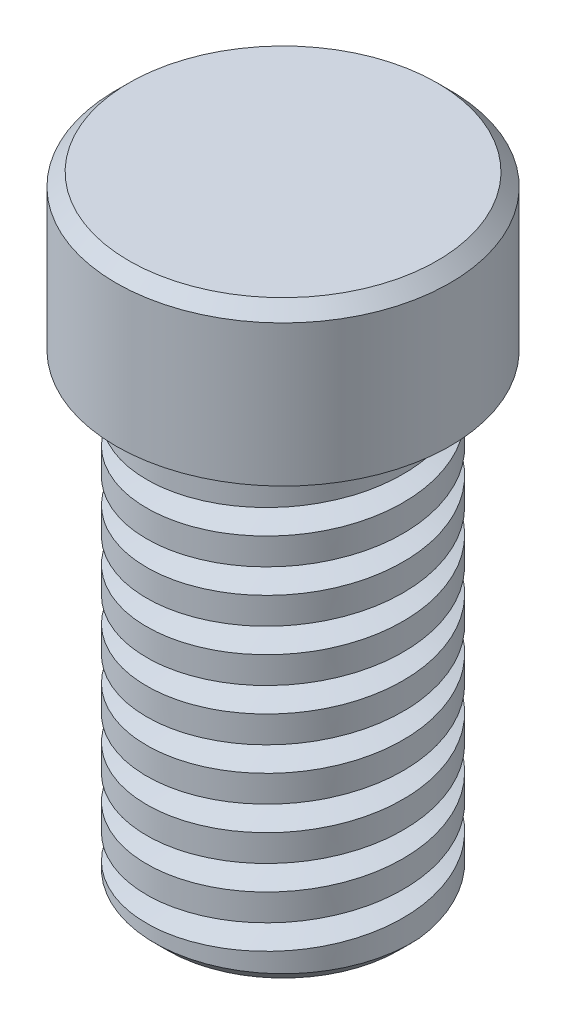
SolidWorks part; units mm, degrees
ref_plane "前视基准面" through (0, 0, 0) normal (0, 0, 1) x (1, 0, 0)
ref_plane "上视基准面" through (0, 0, 0) normal (0, 1, 0) x (1, 0, 0)
ref_plane "右视基准面" through (0, 0, 0) normal (1, 0, 0) x (0, 0, -1)
other "Configuration Table"
sketch "草图1" plane through (0, 0, 0) normal (0, 1, 0) x (1, 0, 0)
  circle A0 centre (0, 0) radius 32.5
  dimension "D1" = 65
extrude "凸台-拉伸1" add sketch "草图1" along normal blind 30
chamfer "倒角1" distance 2.5 angle 45 1 edges at (0, 30, 32.5)
sketch "草图2" plane through (0, 0, 0) normal (0, -1, 0) x (1, 0, 0)
  circle A0 centre (0, 0) radius 25
  dimension "D1" = 50
extrude "凸台-拉伸2" add sketch "草图2" along normal blind 90
sketch "草图4" plane through (0, -90, 0) normal (0, -1, 0) x (1, 0, 0)
  circle A0 centre (0, 0) radius 20
  dimension "D1" = 40
curve "螺旋线/涡状线1" pitch 10 height 85 turns 8.5
sketch "草图5" plane through (0, 0, 0) normal (0, 0, 1) x (1, 0, 0)
  line L0 (-20, -3.9378) -> (-20, -6.0622)
  line L4 (-20, -5) -> (53.068, -5) construction
  line L5 (-20, -3.9378) -> (-27.4169, -1.9505)
  line L6 (-27.4169, -1.9505) -> (-27.4169, -8.0495)
  line L7 (-27.4169, -8.0495) -> (-20, -6.0622)
  spline S1 degree 3 poles (20, -90) (20, -89.8321) (19.3206, -89.4937) (16.3653, -88.9882) (11.77, -88.4821) (5.9952, -87.9762) (-0.3803, -87.4702) (-6.7178, -86.9643) (-12.382, -86.4583) (-16.8055, -85.9524) (-19.5448, -85.4464) (-20.3255, -84.9405) (-19.0693, -84.4345) (-15.9022, -83.9286) (-11.1415, -83.4226) (-5.2643, -82.9167) (1.1405, -82.4107) (7.4309, -81.9048) (12.9767, -81.3988) (17.2221, -80.8929) (19.7417, -80.3869) (20.2828, -79.881) (18.7914, -79.375) (15.4169, -78.869) (10.4975, -78.3631) (4.526, -77.8571) (-1.899, -77.3512) (-8.1337, -76.8452) (-13.5533, -76.3393) (-17.6147, -75.8333) (-19.9109, -75.3274) (-20.2118, -74.8214) (-18.4873, -74.3155) (-14.9101, -73.8095) (-9.8387, -73.3036) (-3.7814, -72.7976) (2.6549, -72.2917) (8.8251, -71.7857) (14.1109, -71.2798) (17.9827, -70.7738) (20.0523, -70.2679) (20.1125, -69.7619) (18.1572, -69.256) (14.3823, -68.75) (9.1662, -68.244) (3.0315, -67.7381) (-3.407, -67.2321) (-9.5041, -66.7262) (-14.6488, -66.2202) (-18.3254, -65.7143) (-20.1657, -65.2083) (-19.9851, -64.7024) (-17.8018, -64.1964) (-13.8345, -63.6905) (-8.4809, -63.1845) (-2.2773, -62.6786) (4.1544, -62.1726) (10.1699, -61.6667) (15.1661, -61.1607) (18.6426, -60.6548) (20.2509, -60.1488) (19.8298, -59.6429) (17.4215, -59.1369) (13.2673, -58.631) (7.7837, -58.125) (1.52, -57.619) (-4.896, -57.1131) (-10.8214, -56.6071) (-15.6623, -56.1012) (-18.9337, -55.5952) (-20.3077, -55.0893) (-19.6467, -54.5833) (-17.0168, -54.0774) (-12.6816, -53.5714) (-7.0756, -53.0655) (-0.7605, -52.5595) (5.6308, -52.0536) (11.4578, -51.5476) (16.1366, -51.0417) (19.1983, -50.5357) (20.3362, -50.0298) (19.4361, -49.5238) (16.5883, -49.0179) (12.0781, -48.5119) (4.4508, -47.8373) (-4.4508, -47.1627) (-12.0781, -46.4881) (-16.5883, -45.9821) (-19.4361, -45.4762) (-20.3362, -44.9702) (-19.1983, -44.4643) (-16.1366, -43.9583) (-11.4578, -43.4524) (-5.6308, -42.9464) (0.7605, -42.4405) (7.0756, -41.9345) (12.6816, -41.4286) (17.0168, -40.9226) (19.6467, -40.4167) (20.3077, -39.9107) (18.9337, -39.4048) (15.6623, -38.8988) (10.8214, -38.3929) (4.896, -37.8869) (-1.52, -37.381) (-7.7837, -36.875) (-13.2673, -36.369) (-17.4215, -35.8631) (-19.8298, -35.3571) (-20.2509, -34.8512) (-18.6426, -34.3452) (-15.1661, -33.8393) (-10.1699, -33.3333) (-4.1544, -32.8274) (2.2773, -32.3214) (8.4809, -31.8155) (13.8345, -31.3095) (17.8018, -30.8036) (19.9851, -30.2976) (20.1657, -29.7917) (18.3254, -29.2857) (14.6488, -28.7798) (9.5041, -28.2738) (3.407, -27.7679) (-3.0315, -27.2619) (-9.1662, -26.756) (-14.3823, -26.25) (-18.1572, -25.744) (-20.1125, -25.2381) (-20.0523, -24.7321) (-17.9827, -24.2262) (-14.1109, -23.7202) (-8.8251, -23.2143) (-2.6549, -22.7083) (3.7814, -22.2024) (9.8387, -21.6964) (14.9101, -21.1905) (18.4873, -20.6845) (20.2118, -20.1786) (19.9109, -19.6726) (17.6147, -19.1667) (13.5533, -18.6607) (8.1337, -18.1548) (1.899, -17.6488) (-4.526, -17.1429) (-10.4975, -16.6369) (-15.4169, -16.131) (-18.7914, -15.625) (-20.2828, -15.119) (-19.7417, -14.6131) (-17.2221, -14.1071) (-12.9767, -13.6012) (-7.4309, -13.0952) (-1.1405, -12.5893) (5.2643, -12.0833) (11.1415, -11.5774) (15.9022, -11.0714) (19.0693, -10.5655) (20.3255, -10.0595) (19.5448, -9.5536) (16.8055, -9.0476) (12.382, -8.5417) (6.7178, -8.0357) (0.3803, -7.5298) (-5.9952, -7.0238) (-11.77, -6.5179) (-16.3653, -6.0118) (-19.3206, -5.5063) (-20, -5.1679) (-20, -5) knots 0 0 0 0 0.005952 0.011905 0.017857 0.02381 0.029762 0.035714 0.041667 0.047619 0.053571 0.059524 0.065476 0.071429 0.077381 0.083333 0.089286 0.095238 0.10119 0.107143 0.113095 0.119048 0.125 0.130952 0.136905 0.142857 0.14881 0.154762 0.160714 0.166667 0.172619 0.178571 0.184524 0.190476 0.196429 0.202381 0.208333 0.214286 0.220238 0.22619 0.232143 0.238095 0.244048 0.25 0.255952 0.261905 0.267857 0.27381 0.279762 0.285714 0.291667 0.297619 0.303571 0.309524 0.315476 0.321429 0.327381 0.333333 0.339286 0.345238 0.35119 0.357143 0.363095 0.369048 0.375 0.380952 0.386905 0.392857 0.39881 0.404762 0.410714 0.416667 0.422619 0.428571 0.434524 0.440476 0.446429 0.452381 0.458333 0.464286 0.470238 0.47619 0.482143 0.488095 0.494048 0.505952 0.511905 0.517857 0.52381 0.529762 0.535714 0.541667 0.547619 0.553571 0.559524 0.565476 0.571429 0.577381 0.583333 0.589286 0.595238 0.60119 0.607143 0.613095 0.619048 0.625 0.630952 0.636905 0.642857 0.64881 0.654762 0.660714 0.666667 0.672619 0.678571 0.684524 0.690476 0.696429 0.702381 0.708333 0.714286 0.720238 0.72619 0.732143 0.738095 0.744048 0.75 0.755952 0.761905 0.767857 0.77381 0.779762 0.785714 0.791667 0.797619 0.803571 0.809524 0.815476 0.821429 0.827381 0.833333 0.839286 0.845238 0.85119 0.857143 0.863095 0.869048 0.875 0.880952 0.886905 0.892857 0.89881 0.904762 0.910714 0.916667 0.922619 0.928571 0.934524 0.940476 0.946429 0.952381 0.958333 0.964286 0.970238 0.97619 0.982143 0.988095 0.994048 1 1 1 1 construction
  dimension "D1" = 30
sweep "切除-扫描3" cut profiles "草图5" path "螺旋线/涡状线1"
chamfer "倒角2" distance 2.5 angle 45 1 edges at (-18.2178, -90, 17.1205)
sketch "草图6" plane through (0, 0, 0) normal (0, 0, 1) x (1, 0, 0)
  line L0 (15, 0) -> (15, -5)
  line L1 (15, -5) -> (56.9861, -5)
  line L2 (56.9861, -5) -> (56.9861, 0)
  line L3 (56.9861, 0) -> (15, 0)
  line L4 (25, -7.5981) -> (25, 0) construction
  line L5 (-32.5, 0) -> (32.5, 0) construction
  line L6 (0, 33.2334) -> (0, -57.5) construction
  spline S0 degree 3 poles (20, -90) (20, -89.8321) (19.3206, -89.4937) (16.3653, -88.9882) (11.77, -88.4821) (5.9952, -87.9762) (-0.3803, -87.4702) (-6.7178, -86.9643) (-12.382, -86.4583) (-16.8055, -85.9524) (-19.5448, -85.4464) (-20.3255, -84.9405) (-19.0693, -84.4345) (-15.9022, -83.9286) (-11.1415, -83.4226) (-5.2643, -82.9167) (1.1405, -82.4107) (7.4309, -81.9048) (12.9767, -81.3988) (17.2221, -80.8929) (19.7417, -80.3869) (20.2828, -79.881) (18.7914, -79.375) (15.4169, -78.869) (10.4975, -78.3631) (4.526, -77.8571) (-1.899, -77.3512) (-8.1337, -76.8452) (-13.5533, -76.3393) (-17.6147, -75.8333) (-19.9109, -75.3274) (-20.2118, -74.8214) (-18.4873, -74.3155) (-14.9101, -73.8095) (-9.8387, -73.3036) (-3.7814, -72.7976) (2.6549, -72.2917) (8.8251, -71.7857) (14.1109, -71.2798) (17.9827, -70.7738) (20.0523, -70.2679) (20.1125, -69.7619) (18.1572, -69.256) (14.3823, -68.75) (9.1662, -68.244) (3.0315, -67.7381) (-3.407, -67.2321) (-9.5041, -66.7262) (-14.6488, -66.2202) (-18.3254, -65.7143) (-20.1657, -65.2083) (-19.9851, -64.7024) (-17.8018, -64.1964) (-13.8345, -63.6905) (-8.4809, -63.1845) (-2.2773, -62.6786) (4.1544, -62.1726) (10.1699, -61.6667) (15.1661, -61.1607) (18.6426, -60.6548) (20.2509, -60.1488) (19.8298, -59.6429) (17.4215, -59.1369) (13.2673, -58.631) (7.7837, -58.125) (1.52, -57.619) (-4.896, -57.1131) (-10.8214, -56.6071) (-15.6623, -56.1012) (-18.9337, -55.5952) (-20.3077, -55.0893) (-19.6467, -54.5833) (-17.0168, -54.0774) (-12.6816, -53.5714) (-7.0756, -53.0655) (-0.7605, -52.5595) (5.6308, -52.0536) (11.4578, -51.5476) (16.1366, -51.0417) (19.1983, -50.5357) (20.3362, -50.0298) (19.4361, -49.5238) (16.5883, -49.0179) (12.0781, -48.5119) (4.4508, -47.8373) (-4.4508, -47.1627) (-12.0781, -46.4881) (-16.5883, -45.9821) (-19.4361, -45.4762) (-20.3362, -44.9702) (-19.1983, -44.4643) (-16.1366, -43.9583) (-11.4578, -43.4524) (-5.6308, -42.9464) (0.7605, -42.4405) (7.0756, -41.9345) (12.6816, -41.4286) (17.0168, -40.9226) (19.6467, -40.4167) (20.3077, -39.9107) (18.9337, -39.4048) (15.6623, -38.8988) (10.8214, -38.3929) (4.896, -37.8869) (-1.52, -37.381) (-7.7837, -36.875) (-13.2673, -36.369) (-17.4215, -35.8631) (-19.8298, -35.3571) (-20.2509, -34.8512) (-18.6426, -34.3452) (-15.1661, -33.8393) (-10.1699, -33.3333) (-4.1544, -32.8274) (2.2773, -32.3214) (8.4809, -31.8155) (13.8345, -31.3095) (17.8018, -30.8036) (19.9851, -30.2976) (20.1657, -29.7917) (18.3254, -29.2857) (14.6488, -28.7798) (9.5041, -28.2738) (3.407, -27.7679) (-3.0315, -27.2619) (-9.1662, -26.756) (-14.3823, -26.25) (-18.1572, -25.744) (-20.1125, -25.2381) (-20.0523, -24.7321) (-17.9827, -24.2262) (-14.1109, -23.7202) (-8.8251, -23.2143) (-2.6549, -22.7083) (3.7814, -22.2024) (9.8387, -21.6964) (14.9101, -21.1905) (18.4873, -20.6845) (20.2118, -20.1786) (19.9109, -19.6726) (17.6147, -19.1667) (13.5533, -18.6607) (8.1337, -18.1548) (1.899, -17.6488) (-4.526, -17.1429) (-10.4975, -16.6369) (-15.4169, -16.131) (-18.7914, -15.625) (-20.2828, -15.119) (-19.7417, -14.6131) (-17.2221, -14.1071) (-12.9767, -13.6012) (-7.4309, -13.0952) (-1.1405, -12.5893) (5.2643, -12.0833) (11.1415, -11.5774) (15.9022, -11.0714) (19.0693, -10.5655) (20.3255, -10.0595) (19.5448, -9.5536) (16.8055, -9.0476) (12.382, -8.5417) (6.7178, -8.0357) (0.3803, -7.5298) (-5.9952, -7.0238) (-11.77, -6.5179) (-16.3653, -6.0118) (-19.3206, -5.5063) (-20, -5.1679) (-20, -5) knots 0 0 0 0 0.005952 0.011905 0.017857 0.02381 0.029762 0.035714 0.041667 0.047619 0.053571 0.059524 0.065476 0.071429 0.077381 0.083333 0.089286 0.095238 0.10119 0.107143 0.113095 0.119048 0.125 0.130952 0.136905 0.142857 0.14881 0.154762 0.160714 0.166667 0.172619 0.178571 0.184524 0.190476 0.196429 0.202381 0.208333 0.214286 0.220238 0.22619 0.232143 0.238095 0.244048 0.25 0.255952 0.261905 0.267857 0.27381 0.279762 0.285714 0.291667 0.297619 0.303571 0.309524 0.315476 0.321429 0.327381 0.333333 0.339286 0.345238 0.35119 0.357143 0.363095 0.369048 0.375 0.380952 0.386905 0.392857 0.39881 0.404762 0.410714 0.416667 0.422619 0.428571 0.434524 0.440476 0.446429 0.452381 0.458333 0.464286 0.470238 0.47619 0.482143 0.488095 0.494048 0.505952 0.511905 0.517857 0.52381 0.529762 0.535714 0.541667 0.547619 0.553571 0.559524 0.565476 0.571429 0.577381 0.583333 0.589286 0.595238 0.60119 0.607143 0.613095 0.619048 0.625 0.630952 0.636905 0.642857 0.64881 0.654762 0.660714 0.666667 0.672619 0.678571 0.684524 0.690476 0.696429 0.702381 0.708333 0.714286 0.720238 0.72619 0.732143 0.738095 0.744048 0.75 0.755952 0.761905 0.767857 0.77381 0.779762 0.785714 0.791667 0.797619 0.803571 0.809524 0.815476 0.821429 0.827381 0.833333 0.839286 0.845238 0.85119 0.857143 0.863095 0.869048 0.875 0.880952 0.886905 0.892857 0.89881 0.904762 0.910714 0.916667 0.922619 0.928571 0.934524 0.940476 0.946429 0.952381 0.958333 0.964286 0.970238 0.97619 0.982143 0.988095 0.994048 1 1 1 1 construction
  dimension "D1" = 10
  dimension "D2" = 5
revolve "切除-旋转1" cut sketch "草图6" angle 360 about L6
